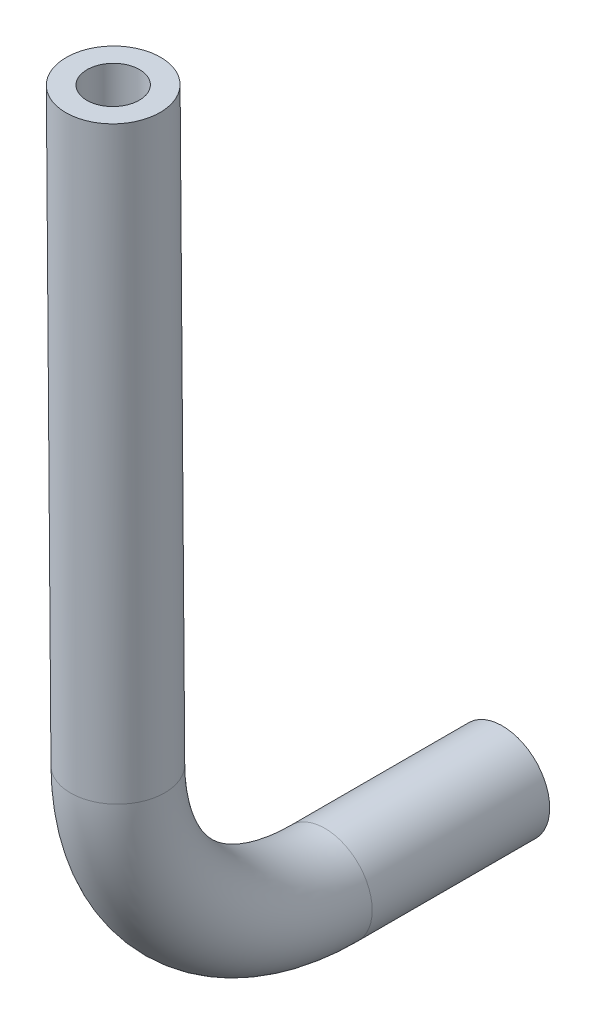
SolidWorks part; units mm, degrees
material "1.4404 (X2CrNiMo17-12-2)"
ref_plane "Ebene vorne" through (0, 0, 0) normal (0, 0, 1) x (1, 0, 0)
ref_plane "Ebene oben" through (0, 0, 0) normal (0, 1, 0) x (1, 0, 0)
ref_plane "Ebene rechts" through (0, 0, 0) normal (1, 0, 0) x (0, 0, -1)
sketch "Sketch1" plane through (0, 0, 0) normal (0, 0, 1) x (1, 0, 0)
  circle A0 centre (0, 0) radius 1.6
  circle A1 centre (0, 0) radius 0.89
  dimension "D1" = 3.2
  dimension "D2" = 0.71
sketch "Sketch2" plane through (0, 0, 0) normal (1, 0, 0) x (0, 0, -1)
  arc A0 (0, 0) -> (-6.9998, 6.9449) centre (0, 7) cw
sweep "Sweep1" add profiles "Sketch1" path "Sketch2"
extrude "Boss-Extrude1" add sketch "Sketch1<2>" against normal blind 6
sketch "Sketch1<2>" plane through (0, 0, 0) normal (0, 0, 1) x (1, 0, 0) same geometry as "Sketch1"
sketch "Sketch5" plane through (0, 6.9996, 0.0551) normal (0, 1, 0.0079) x (1, 0, 0)
  circle A0 centre (0, -6.9449) radius 0.89
  circle A1 centre (0, -6.9449) radius 1.6
extrude "Boss-Extrude2" add sketch "Sketch5" along normal blind 20
